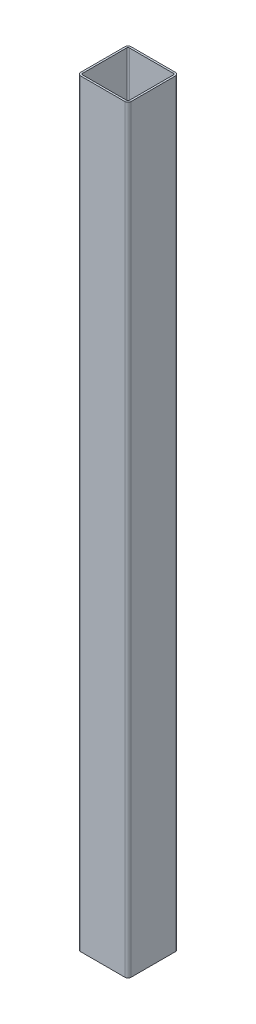
SolidWorks part; units mm, degrees
ref_plane "Спереди" through (0, 0, 0) normal (0, 0, 1) x (1, 0, 0)
ref_plane "Сверху" through (0, 0, 0) normal (0, 1, 0) x (1, 0, 0)
ref_plane "Справа" through (0, 0, 0) normal (1, 0, 0) x (0, 0, -1)
sketch "Эскиз1" plane through (0, 0, 0) normal (0, 1, 0) x (1, 0, 0)
  line L1 (-35, 40) -> (35, 40)
  line L2 (-40, 35) -> (-40, -35)
  line L3 (-35, -40) -> (35, -40)
  line L4 (40, 35) -> (40, -35)
  line L5 (-40, 40) -> (40, -40) construction
  line L6 (-40, -40) -> (40, 40) construction
  arc A0 (35, -40) -> (40, -35) centre (35, -35) ccw
  arc A1 (35, 40) -> (40, 35) centre (35, 35) cw
  arc A2 (-35, 40) -> (-40, 35) centre (-35, 35) ccw
  arc A3 (-40, -35) -> (-35, -40) centre (-35, -35) ccw
  point P0 (0, 0)
  dimension "D1" = 5
extrude "Вытянуть-Тонкостенный1" add sketch "Эскиз1" along normal blind 1200 thin thin type one direction reverse wall 3
ref_axis "Ось1" through (0, -50, 0) along (0, 1, 0)
